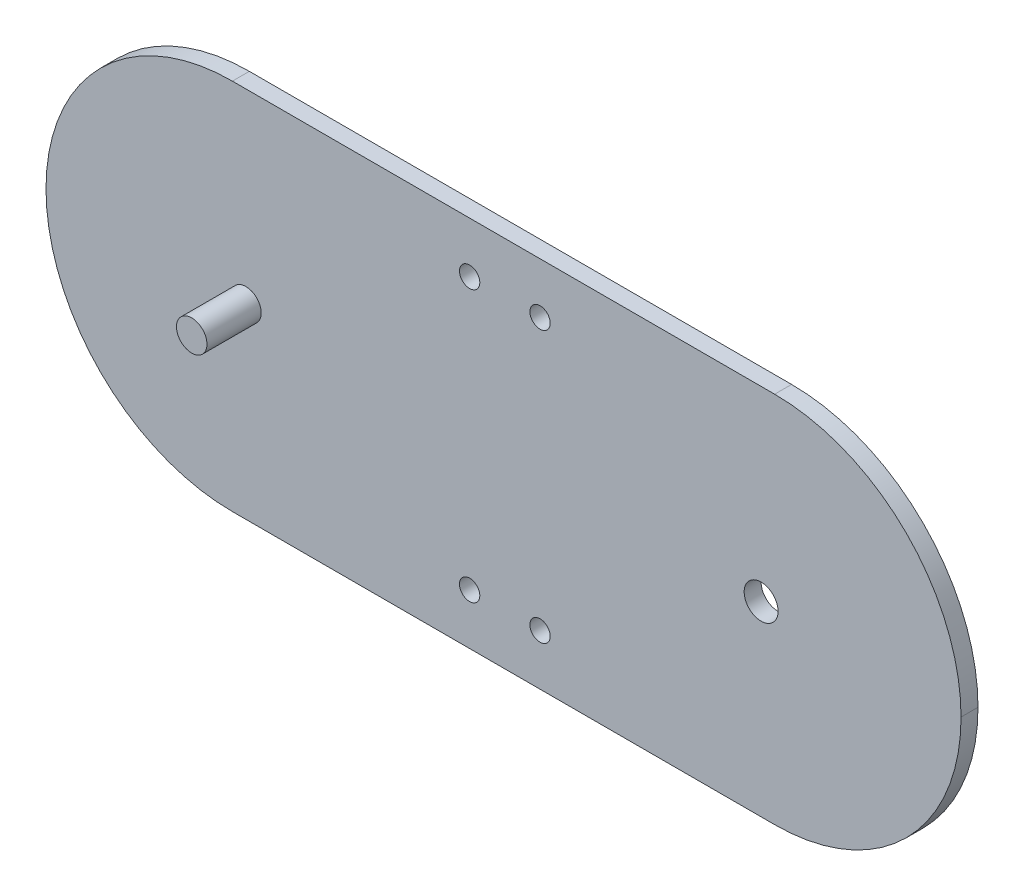
SolidWorks part; units mm, degrees
ref_plane "Front Plane" through (0, 0, 0) normal (0, 0, 1) x (1, 0, 0)
ref_plane "Top Plane" through (0, 0, 0) normal (0, 1, 0) x (1, 0, 0)
ref_plane "Right Plane" through (0, 0, 0) normal (1, 0, 0) x (0, 0, -1)
sketch "Sketch1" plane through (0, 0, 0) normal (0, 0, 1) x (1, 0, 0)
  line L1 (67.5, 27.5) -> (-67.5, 27.5)
  line L2 (67.5, 27.5) -> (67.5, -27.5)
  line L3 (67.5, -27.5) -> (-67.5, -27.5)
  line L4 (-67.5, 27.5) -> (-67.5, -27.5)
  line L5 (67.5, 27.5) -> (-67.5, -27.5) construction
  line L6 (67.5, -27.5) -> (-67.5, 27.5) construction
  point P0 (0, 0)
  dimension "D1" = 55
  dimension "D2" = 135
extrude "Boss-Extrude1" add sketch "Sketch1" along normal blind 2.5
fillet "Fillet1" radius 27.5 4 edges at (-67.5, -27.5, 1.25) (-67.5, 27.5, 1.25) (67.5, -27.5, 1.25) (67.5, 27.5, 1.25)
sketch "Sketch2" plane through (0, 0, 2.5) normal (0, 0, 1) x (1, 0, 0)
  line L0 (0, 0) -> (0, 20)
  line L1 (0, 20) -> (-5, 20)
  line L2 (-5, 20) -> (5.39, 20)
  circle A0 centre (-5, 20) radius 1.5
  circle A1 centre (5.39, 20) radius 1.5
  dimension "D4" = 3
  dimension "D5" = 3
  dimension "D1" = 20
  dimension "D2" = 5
  dimension "D3" = 10.39
extrude "Cut-Extrude1" cut sketch "Sketch2" against normal blind 2.5 contours A0 | A1 region at (-6.4576, 20, 2.5) region at (5.39, 21.4576, 2.5)
mirror "Mirror1" about plane through (0, 0, 0) normal (0, 1, 0) of "Cut-Extrude1"
sketch "Sketch3" plane through (0, 0, 0) normal (0, 0, -1) x (-1, 0, 0)
  line L0 (0, 0) -> (-38, 0)
  circle A0 centre (-38, 0) radius 2.5
  dimension "D2" = 5
  dimension "D1" = 38
extrude "Cut-Extrude2" cut sketch "Sketch3" against normal blind 2.5 contours A0 region at (40.4293, 0, 0)
sketch "Sketch4" plane through (0, 0, 2.5) normal (0, 0, 1) x (1, 0, 0)
  line L0 (0, 0) -> (-38, 0)
  circle A0 centre (-38, 0) radius 2.25
  dimension "D2" = 4.5
  dimension "D1" = 38
extrude "Boss-Extrude2" add sketch "Sketch4" along normal blind 8 contours A0 region at (-40.1864, 0, 2.5)
